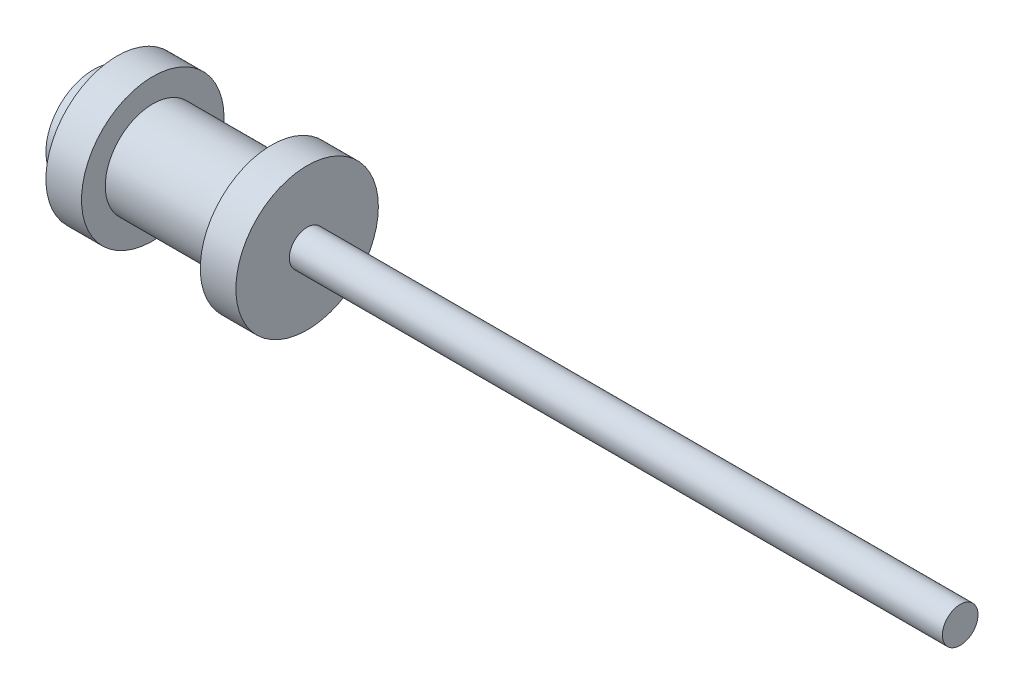
SolidWorks part; units mm, degrees
ref_plane "Front Plane" through (0, 0, 0) normal (0, 0, 1) x (1, 0, 0)
ref_plane "Top Plane" through (0, 0, 0) normal (0, 1, 0) x (1, 0, 0)
ref_plane "Right Plane" through (0, 0, 0) normal (1, 0, 0) x (0, 0, -1)
sketch "Sketch1" plane through (0, 0, 0) normal (0, 0, 1) x (1, 0, 0)
  line L0 (0, -4) -> (0, -6)
  line L1 (0, -6) -> (3, -6)
  line L2 (3, -6) -> (3, -4)
  line L3 (3, -4) -> (13, -4)
  line L4 (13, -4) -> (13, -6)
  line L5 (13, -6) -> (16, -6)
  line L6 (16, -6) -> (16, -1.5)
  line L7 (16, -1.5) -> (71, -1.5)
  line L8 (71, -1.5) -> (71, 0)
  line L9 (71, 0) -> (0, 0)
  line L10 (0, 0) -> (-2, 0)
  line L11 (-2, 0) -> (-2, -4)
  line L12 (-2, -4) -> (0, -4)
  point P3 (0, 0)
  dimension "D1" = 3
  dimension "D2" = 3
  dimension "D3" = 10
  dimension "D4" = 55
  dimension "D5" = 1.5
  dimension "D6" = 6
  dimension "D7" = 4
  dimension "D8" = 2
revolve "Revolve1" add sketch "Sketch1" angle 360 about L9
